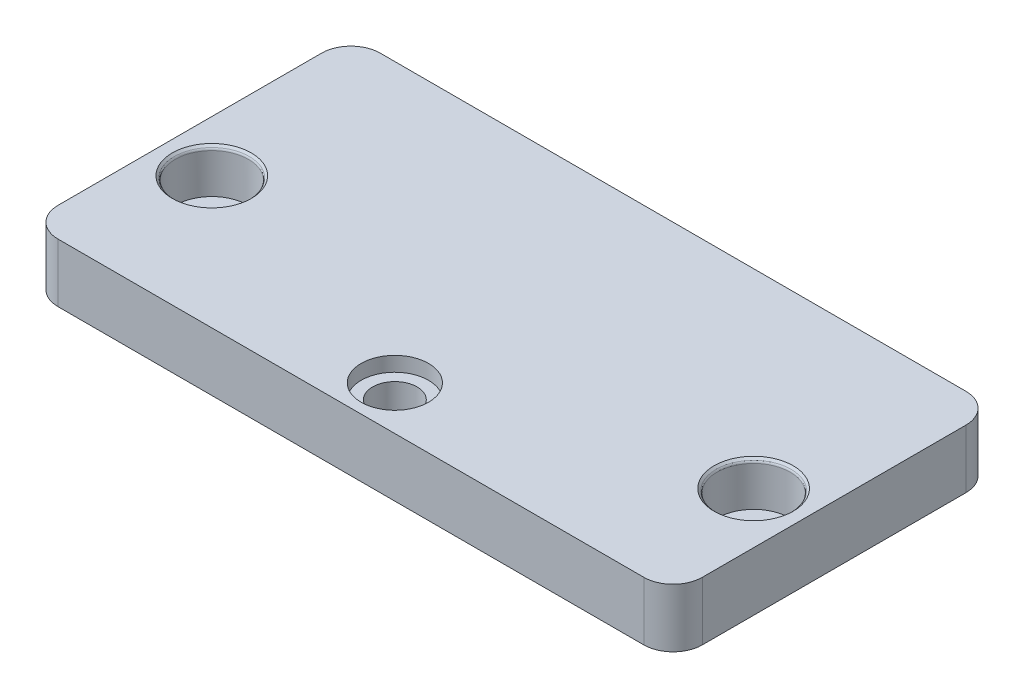
SolidWorks part; units mm, degrees
ref_plane "Front Plane" through (0, 0, 0) normal (0, 0, 1) x (1, 0, 0)
ref_plane "Top Plane" through (0, 0, 0) normal (0, 1, 0) x (1, 0, 0)
ref_plane "Right Plane" through (0, 0, 0) normal (1, 0, 0) x (0, 0, -1)
sketch "Sketch1" plane through (0, 0, 0) normal (0, 1, 0) x (1, 0, 0)
  line L1 (0, 0) -> (220, 0)
  line L2 (0, 0) -> (0, 110)
  line L3 (0, 110) -> (220, 110)
  line L4 (220, 0) -> (220, 110)
  dimension "D1" = 220
  dimension "D2" = 110
extrude "Boss-Extrude1" add sketch "Sketch1" along normal blind 20
sketch "Sketch2" plane through (0, 20, 0) normal (0, 1, 0) x (1, 0, 0)
  line L0 (0, 45) -> (220, 45) construction
  line L1 (0, 110) -> (0, 0) construction
  line L2 (220, 0) -> (220, 110) construction
  line L3 (0, 0) -> (220, 0) construction
  line L4 (110, 45) -> (110, 110) construction
  line L5 (220, 110) -> (0, 110) construction
  circle A0 centre (17.5, 45) radius 12.49
  circle A1 centre (202.5, 45) radius 12.49
  circle A2 centre (110, 15) radius 7.6
  point P10 (110, 45)
  dimension "D2" = 24.98
  dimension "D4" = 15
  dimension "D5" = 15.2
  dimension "D1" = 45
  dimension "D3" = 92.5
extrude "Cut-Extrude1" cut sketch "Sketch2" against normal blind 15
chamfer "Chamfer1" distance 1 angle 45 2 edges at (202.5, 20, -57.49) (17.5, 20, -32.51)
fillet "Fillet1" radius 1 2 edges at (202.5, 19, -57.49) (17.5, 19, -57.49)
sketch "Sketch4" plane through (0, 20, 0) normal (0, 1, 0) x (1, 0, 0)
  circle A0 centre (110, 15) radius 11.5
  dimension "D1" = 23
extrude "Cut-Extrude2" cut sketch "Sketch4" against normal blind 5
fillet "Fillet2" radius 10 4 edges at (220, 10, -110) (220, 10, 0) (0, 10, 0) (0, 10, -110)
